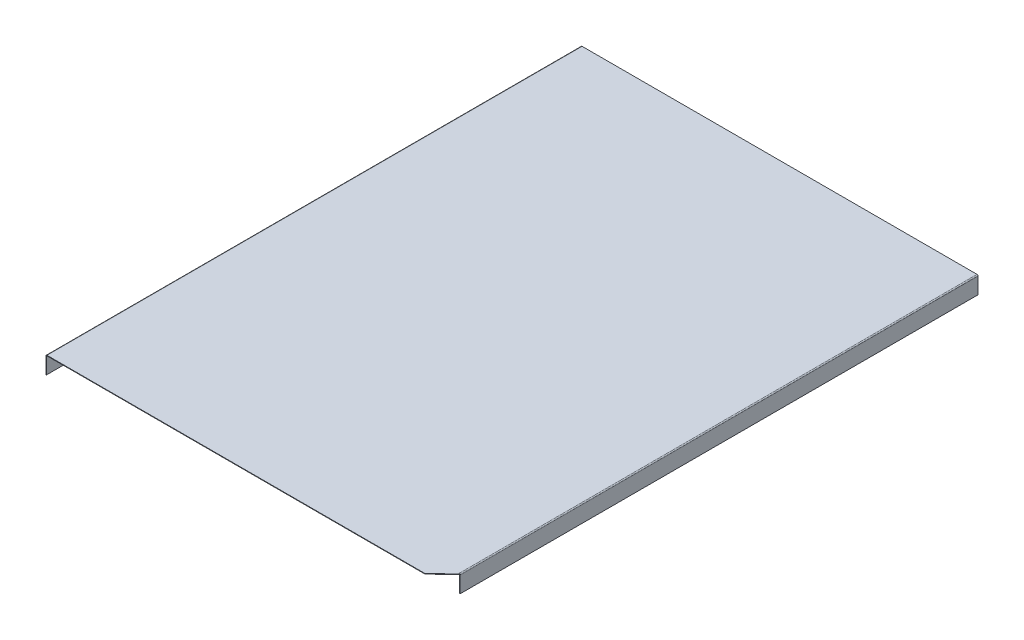
SolidWorks part; units mm, degrees
note: The reader was unsure of these and kept them because the rebuilt part matched: flange length of "Edge-Flange1".
material "AISI 1020 Steel, Cold Rolled"
ref_plane "Front Plane" through (0, 0, 0) normal (0, 0, 1) x (1, 0, 0)
ref_plane "Top Plane" through (0, 0, 0) normal (0, 1, 0) x (1, 0, 0)
ref_plane "Right Plane" through (0, 0, 0) normal (1, 0, 0) x (0, 0, -1)
sketch "Sketch1" plane through (0, 0, 0) normal (0, 1, 0) x (1, 0, 0)
  line L1 (-473.7, -638.7) -> (473.7, -638.7)
  line L2 (-473.7, -638.7) -> (-473.7, 638.7)
  line L3 (-473.7, 638.7) -> (473.7, 638.7)
  line L4 (473.7, -638.7) -> (473.7, 638.7)
  line L5 (-473.7, -638.7) -> (473.7, 638.7) construction
  line L6 (-473.7, 638.7) -> (473.7, -638.7) construction
  point P0 (0, 0)
  dimension "D1" = 1277.4
  dimension "D2" = 947.4
sheet metal parameters "Sheet-Metal1" thickness 1.2 parameters "D1"=0.7366
base flange "Base-Flange1" sketch "Sketch1" thickness 1.2 reverse thickness direction no parameters "D1"=0.7366
sketch "Sketch3" plane through (0, -1.2, 0) normal (0, -1, 0) x (1, 0, 0)
  line L0 (431.3, 638.7) -> (512.4055, 658.6055)
  line L1 (-473.7, 638.7) -> (473.7, 638.7) construction
  line L2 (512.4055, 658.6055) -> (473.7, 597.5)
  line L3 (473.7, 638.7) -> (473.7, -638.7) construction
  line L4 (431.3, 638.7) -> (473.7, 597.5)
  dimension "D1" = 42.4
  dimension "D2" = 41.2
extrude "Cut-Extrude1" cut sketch "Sketch3" against normal blind 10 normal cut yes
edge flange "Edge-Flange1" sketch "Sketch8" flange profiles "Sketch8", "Sketch9" flange angle 90 flange length 41.2 flange position material inside bend radius 1.2 thickness 1.2 relief none parameters "D6"=10, "D8"=0.1
sketch "Sketch8" plane through (473.7, -1.2, 0) normal (1, 0, 0) x (0, 0, 1)
  line L2 (-638.7, 0) -> (-638.7, 40)
  line L3 (-638.7, 40) -> (597.5, 40)
  line L4 (597.5, 40) -> (597.5, 0)
  line L5 (597.5, 0) -> (-638.7, 0) construction
  line L6 (597.5, 0) -> (-638.7, 0)
sketch "Sketch9" plane through (-473.7, -1.2, 0) normal (-1, 0, 0) x (0, 0, -1)
  line L0 (638.7, 0) -> (-638.7, 0) construction
  line L1 (638.7, 0) -> (-638.7, 0)
  line L2 (-638.7, 0) -> (-638.7, 40)
  line L3 (-638.7, 40) -> (638.7, 40)
  line L4 (638.7, 40) -> (638.7, 0)
bend "EdgeBend1" bend radius 1.2 bend angle 90 parameters "D5"=1
bend "EdgeBend2" bend radius 1.2 bend angle 90 parameters "D5"=2
flat pattern "Flat-Pattern1" [suppressed]
sketch "Bend-Lines1" plane through (0, 0, 0) normal (0, 1, 0) x (-1, 0, 0)
bend of the flat pattern "Flatten-<EdgeBend1>1"
bend of the flat pattern "Flatten-<EdgeBend2>1"
